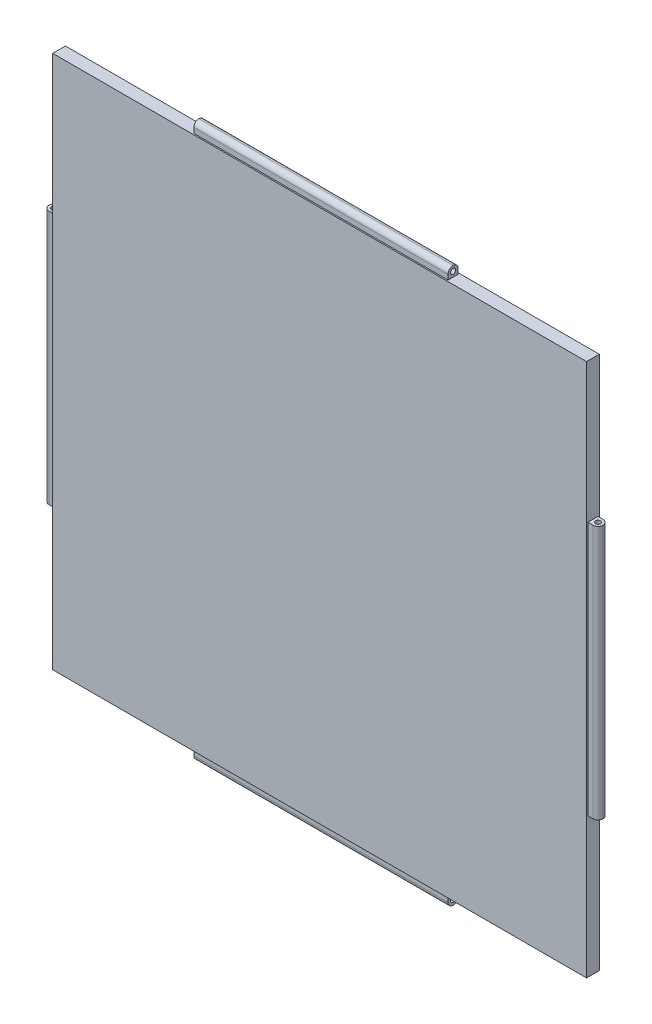
SolidWorks part; units mm, degrees
ref_plane "前视基准面" through (0, 0, 0) normal (0, 0, 1) x (1, 0, 0)
ref_plane "上视基准面" through (0, 0, 0) normal (0, 1, 0) x (1, 0, 0)
ref_plane "右视基准面" through (0, 0, 0) normal (1, 0, 0) x (0, 0, -1)
other "Configuration Table"
sketch "草图1" plane through (0, 0, 0) normal (0, 0, 1) x (1, 0, 0)
  line L1 (-210, -210) -> (210, -210)
  line L2 (-210, -210) -> (-210, 210)
  line L3 (-210, 210) -> (210, 210)
  line L4 (210, -210) -> (210, 210)
  line L5 (-210, -210) -> (210, 210) construction
  line L6 (-210, 210) -> (210, -210) construction
  point P0 (0, 0)
  dimension "D1" = 420
  dimension "D2" = 420
extrude "凸台-拉伸1" add sketch "草图1" along normal blind 10 contours L2 L1 L4 L3
sketch "草图2" plane through (0, 210, 0) normal (0, 1, 0) x (1, 0, 0)
  line L0 (-210, -5) -> (210, -5) construction
  line L1 (0, 0) -> (0, -10) construction
  line L3 (100, -1) -> (-100, -1)
  line L4 (210, 0) -> (-210, 0)
  line L5 (-210, 0) -> (-210, -10)
  line L6 (-210, -10) -> (210, -10)
  line L7 (210, -10) -> (210, 0)
  line L8 (210, 0) -> (-210, 0)
  line L9 (-210, 0) -> (-210, -10)
  line L10 (-210, -10) -> (210, -10)
  line L11 (210, -10) -> (210, 0)
  line L12 (100, -1) -> (100, -9)
  line L13 (100, -9) -> (-100, -9)
  line L14 (-100, -1) -> (-100, -9)
  line L15 (100, -1) -> (-100, -9) construction
  line L16 (100, -9) -> (-100, -1) construction
  point P6 (0, -5)
  dimension "D2" = 200
  dimension "D3" = 8
  dimension "D1" = 0
extrude "凸台-拉伸2" add sketch "草图2" along normal blind 8 contours L12 L3 L14 L13
sketch "草图3" plane through (100, 0, 0) normal (1, 0, 0) x (0, 0, -1)
  line L0 (-10, 210) -> (0, 210) construction
  line L1 (-1, 218) -> (-1, 210) construction
  circle A0 centre (-5, 214) radius 2
  dimension "D1" = 4
  dimension "D2" = 4
  dimension "D3" = 4
extrude "切除-拉伸1" cut sketch "草图3" against normal up to next contours A0
fillet "圆角1" radius 4 2 edges at (0, 218, 1) (0, 218, 9)
mirror "镜向1" about plane through (0, 0, 0) normal (0, 1, 0) of "圆角1", "凸台-拉伸2", "凸台-拉伸1", "切除-拉伸1"
sketch "草图4" plane through (-210, 0, 0) normal (-1, 0, 0) x (0, 0, 1)
  line L0 (0, 0) -> (10, 0) construction
  line L1 (10, -210) -> (10, 210) construction
  line L3 (1, 100) -> (9, 100)
  line L4 (1, 100) -> (1, -100)
  line L5 (1, -100) -> (9, -100)
  line L6 (9, 100) -> (9, -100)
  line L7 (1, 100) -> (9, -100) construction
  line L8 (1, -100) -> (9, 100) construction
  point P5 (5, 0)
  dimension "D1" = 200
  dimension "D2" = 8
extrude "凸台-拉伸3" add sketch "草图4" along normal blind 8 contours L4 L3 L6 L5
fillet "圆角2" radius 4 2 edges at (-218, 0, 9) (-218, 0, 1)
sketch "草图5" plane through (0, -100, 0) normal (0, -1, 0) x (1, 0, 0)
  line L0 (-210, 10) -> (-210, 0) construction
  line L1 (-214, 9) -> (-210, 9) construction
  circle A0 centre (-214, 5) radius 2
  dimension "D1" = 4
  dimension "D2" = 4
  dimension "D3" = 4
extrude "切除-拉伸2" cut sketch "草图5" against normal up to next
mirror "镜向3" about plane through (0, 0, 0) normal (1, 0, 0) of "切除-拉伸2", "凸台-拉伸3", "圆角2"
